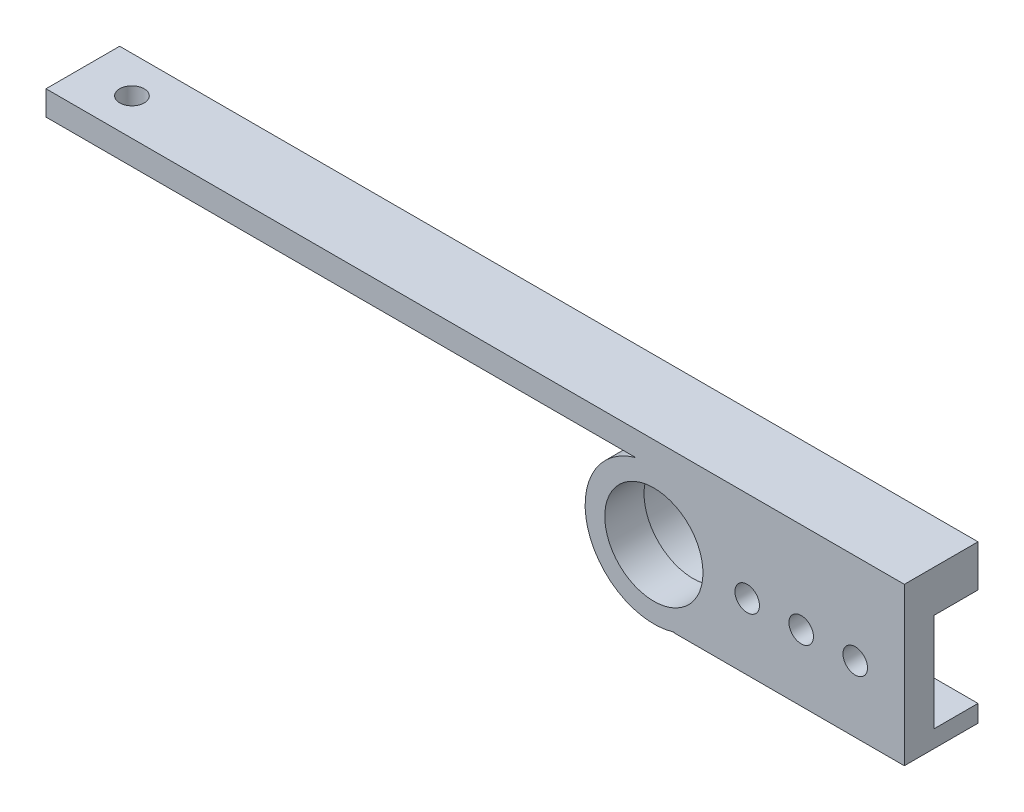
SolidWorks part; units mm, degrees
ref_plane "前视基准面" through (0, 0, 0) normal (0, 0, 1) x (1, 0, 0)
ref_plane "上视基准面" through (0, 0, 0) normal (0, 1, 0) x (1, 0, 0)
ref_plane "右视基准面" through (0, 0, 0) normal (1, 0, 0) x (0, 0, -1)
sketch "草图1" plane through (0, 0, 0) normal (0, 0, 1) x (1, 0, 0)
  line L1 (20, -10) -> (-20, -10)
  line L2 (20, -10) -> (20, 10)
  line L3 (20, 10) -> (-20, 10)
  line L4 (-20, -10) -> (-20, 10)
  line L5 (20, -10) -> (-20, 10) construction
  line L6 (20, 10) -> (-20, -10) construction
  point P0 (0, 0)
  dimension "D1" = 40
  dimension "D2" = 20
extrude "凸台-拉伸1" add sketch "草图1" along normal blind 6
sketch "草图2" plane through (0, 0, 6) normal (0, 0, 1) x (1, 0, 0)
  line L0 (20, -10) -> (20, 10) construction
  circle A0 centre (10, 0) radius 2.5
  circle A1 centre (-1, 0) radius 2.5
  circle A2 centre (-12, 0) radius 2.5
  dimension "D1" = 10
  dimension "D2" = 5
  dimension "D3" = 3
extrude "切除-拉伸1" cut sketch "草图2" against normal through all
sketch "草图3" plane through (0, 0, 6) normal (0, 0, 1) x (1, 0, 0)
  line L0 (20, 13.5) -> (20, 10)
  line L1 (20, -13.5) -> (-26.894, -13.5)
  line L3 (20, 13.5) -> (-26.894, 13.5)
  line L4 (-20, 10) -> (-20, -10)
  line L5 (-20, -10) -> (20, -10)
  line L6 (20, -10) -> (20, 10)
  line L7 (20, 10) -> (-20, 10)
  line L8 (-20, 10) -> (-20, -10)
  line L9 (-20, -10) -> (20, -10)
  line L10 (20, -10) -> (20, 10)
  line L11 (20, 10) -> (-20, 10)
  line L12 (-26.894, -13.5) -> (-26.894, 13.5)
  line L13 (20, -10.0394) -> (-26.894, 13.5) construction
  line L14 (20, 10.0394) -> (-26.894, -13.5) construction
  line L15 (20, -10) -> (20, -13.5)
  circle A0 centre (-31, 0) radius 11
  circle A1 centre (-31, 0) radius 14
  point P2 (0, 0)
  line M10 (-20, 10) -> (-20, -10)
  line M11 (-20, -10) -> (20, -10)
  line M13 (20, 10) -> (-20, 10)
  dimension "D3" = 22
  dimension "D4" = 28
  dimension "D2" = 3.5
  dimension "D1" = 0
extrude "凸台-拉伸2" add sketch "草图3" against normal blind 15 contours L3 A1 L1 L12 A0 | A1 L1 L15 M11 M10 | L1 A1 L8 A0 L12 | L8 A1 L3 L12 A0 | L8 A1 | A1 L0 L3 M10 M13 region at (-1.9449, 11.7771, 6) region at (-1.9449, -11.7771, 6) region at (-23.0173, 9.0328, 6) region at (-27.2274, 11.7946, 6) region at (-18.7882, 0, 6) region at (-23.0173, -9.0328, 6)
sketch "草图5" plane through (0, 0, 6) normal (0, 0, 1) x (1, 0, 0)
  circle A0 centre (-31, 0) radius 10
  circle A1 centre (-31, 0) radius 11 construction
  circle A2 centre (-31, 0) radius 11
  dimension "D1" = 20
extrude "凸台-拉伸3" add sketch "草图5" against normal blind 8
sketch "草图6" plane through (0, 0, 6) normal (0, 0, 1) x (1, 0, 0)
  circle A0 centre (-31, 0) radius 8.5
  circle A1 centre (-31, 0) radius 10 construction
  circle A2 centre (-31, 0) radius 10
  dimension "D1" = 17
sketch "草图7" plane through (0, 13.5, 0) normal (0, 1, 0) x (1, 0, 0)
  circle A0 centre (-16.8213, 3.0525) radius 3.3366
sketch "草图8" plane through (20, 0, 0) normal (1, 0, 0) x (0, 0, -1)
  line L1 (-6, 13.5) -> (9, 13.5)
  line L2 (-6, 13.5) -> (-6, 18.5)
  line L3 (-6, 18.5) -> (9, 18.5)
  line L4 (9, 13.5) -> (9, 18.5)
  dimension "D1" = 5
extrude "凸台-拉伸4" add sketch "草图8" against normal blind 200
sketch "草图9" plane through (0, 0, 6) normal (0, 0, 1) x (1, 0, 0)
  line L1 (-29.5663, 15.6648) -> (-25.1627, 15.6648)
  line L2 (-29.5663, 15.6648) -> (-29.5663, 11.9284)
  line L3 (-29.5663, 11.9284) -> (-25.1627, 11.9284)
  line L4 (-25.1627, 15.6648) -> (-25.1627, 11.9284)
extrude "凸台-拉伸5" add sketch "草图9" against normal through all
sketch "草图11" plane through (0, 18.5, 0) normal (0, 1, 0) x (1, 0, 0)
  line L0 (-118.4338, -6) -> (-118.4338, 9)
  line L1 (-180, -6) -> (20, -6) construction
  line L2 (-118.4338, 246.7017) -> (-118.4338, -123.2983) construction
  line L3 (-180, 9) -> (20, 9) construction
sketch "草图13" plane through (0, 18.5, 0) normal (0, 1, 0) x (1, 0, 0)
  line L1 (-118.4338, -6) -> (-183.1111, -6)
  line L2 (-118.4338, -6) -> (-118.4338, 12.5245)
  line L3 (-118.4338, 12.5245) -> (-183.1111, 12.5245)
  line L4 (-183.1111, -6) -> (-183.1111, 12.5245)
extrude "切除-拉伸2" cut sketch "草图13" against normal through all
sketch "草图14" plane through (0, 18.5, 0) normal (0, 1, 0) x (1, 0, 0)
  line L0 (-154.7729, 11.0465) -> (-154.7729, -39.4434)
  line L1 (-154.7729, 244.91) -> (-154.7729, -125.09) construction
sketch "草图15" plane through (0, 18.5, 0) normal (0, 1, 0) x (1, 0, 0)
  line L0 (-154.7729, 11.0465) -> (-154.7729, -39.4434) construction
  line L1 (-118.4338, -6) -> (-154.7729, -6)
  line L2 (-118.4338, -6) -> (-118.4338, 9)
  line L3 (-118.4338, 9) -> (-154.7729, 9)
  line L4 (-154.7729, -6) -> (-154.7729, 9)
extrude "凸台-拉伸6" add sketch "草图15" against normal blind 5
sketch "草图16" plane through (0, 18.5, 0) normal (0, 1, 0) x (1, 0, 0)
  line L0 (-154.7729, 9) -> (-154.7729, -6)
  line L1 (-154.7729, 1.5) -> (-144.7729, 1.5) construction
  circle A0 centre (-144.7729, 1.5) radius 2.5
  dimension "D1" = 5
  dimension "D2" = 10
extrude "切除-拉伸3" cut sketch "草图16" against normal through all contours A0 region at (-144.7729, 18.5, -1.5)
